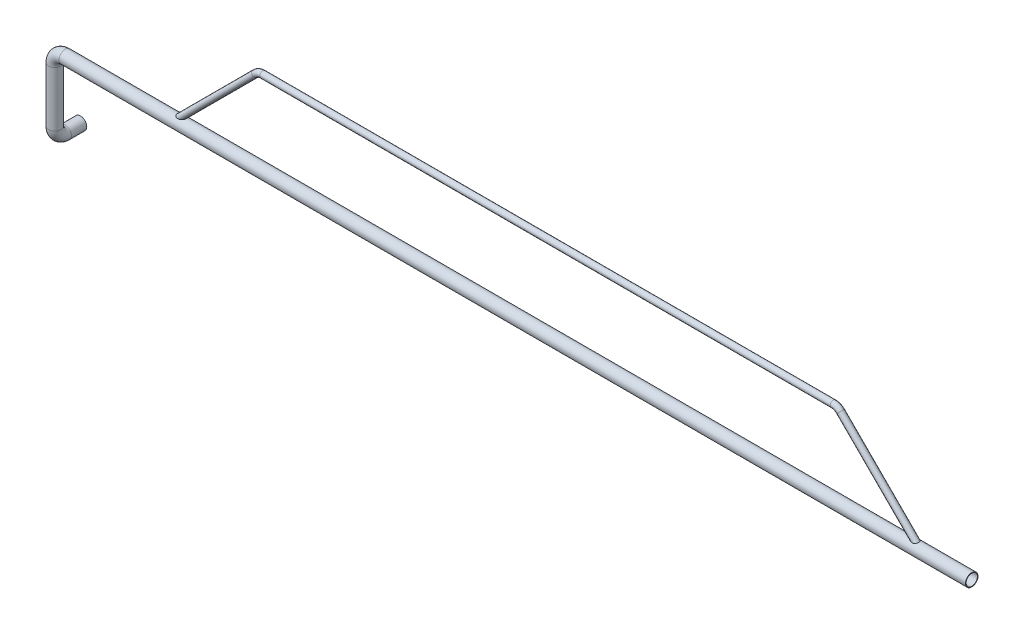
SolidWorks part; units mm, degrees
ref_plane "Plano frontal" through (0, 0, 0) normal (0, 0, 1) x (1, 0, 0)
ref_plane "Plano superior" through (0, 0, 0) normal (0, 1, 0) x (1, 0, 0)
ref_plane "Plano direito" through (0, 0, 0) normal (1, 0, 0) x (0, 0, -1)
sketch3d "3DSketch1"
  line L0 (-24893.0062, -8356.2045, 38950.2493) -> (-29246.5547, -8356.2045, 38950.2493)
  line L3 (-29296.5547, -8406.2045, 38950.2493) -> (-29296.5547, -8670.5186, 38950.2493)
  line L4 (-29296.5547, -8720.5186, 38900.2493) -> (-29296.5547, -8720.5186, 38826.8902)
  line L5 (-29296.5547, -8720.5186, 38826.8902) -> (-29296.5547, -8720.5186, 38797.8902) construction
  arc A0 (-29296.5547, -8720.5186, 38900.2493) -> (-29296.5547, -8670.5186, 38950.2493) centre (-29296.5547, -8670.5186, 38900.2493) ccw
  arc A1 (-29296.5547, -8406.2045, 38950.2493) -> (-29246.5547, -8356.2045, 38950.2493) centre (-29246.5547, -8406.2045, 38950.2493) ccw
  point P12 (-29296.5547, -8720.5186, 38950.2493)
  point P13 (-29346.5547, -8670.5186, 38900.2493)
  point P16 (-29296.5547, -8356.2045, 38950.2493)
  point P17 (-29246.5547, -8406.2045, 38900.2493)
  dimension "D1" = 50
sweep "Sweep-Thin1" add path "3DSketch1" circular profile diameter 60 parameters "D1"=3, "D3"=60
sketch3d "3DSketch2"
  line L0 (-25137.3745, -8356.2045, 38950.2493) -> (-25522.7298, -7970.8492, 38950.2493)
  line L1 (-24893.0062, -8356.2045, 38950.2493) -> (-29246.5547, -8356.2045, 38950.2493) construction
  line L2 (-25558.0851, -7956.2045, 38950.2493) -> (-28297.4869, -7956.2045, 38950.2493)
  line L3 (-28332.8423, -7970.8492, 38950.2493) -> (-28718.1976, -8356.2045, 38950.2493)
  line L6 (-25693.0803, -7956.2045, 38950.2493) -> (-25693.0803, -8356.2045, 38950.2493) construction
  arc A0 (-28297.4869, -7956.2045, 38950.2493) -> (-28332.8423, -7970.8492, 38950.2493) centre (-28297.4869, -8006.2045, 38950.2493) ccw
  arc A1 (-25558.0851, -7956.2045, 38950.2493) -> (-25522.7298, -7970.8492, 38950.2493) centre (-25558.0851, -8006.2045, 38950.2493) ccw
  point P17 (-28318.1976, -7956.2045, 38950.2493)
  point P18 (-28297.4869, -8006.2045, 39000.2493)
  point P21 (-25537.3745, -7956.2045, 38950.2493)
  point P22 (-25558.0851, -8006.2045, 38900.2493)
  dimension "D4" = 50
  dimension "D1" = 135
  dimension "D2" = 135
  dimension "D3" = 400
sweep "Sweep-Thin2" add path "3DSketch2" circular profile diameter 30 parameters "D1"=3, "D3"=30
